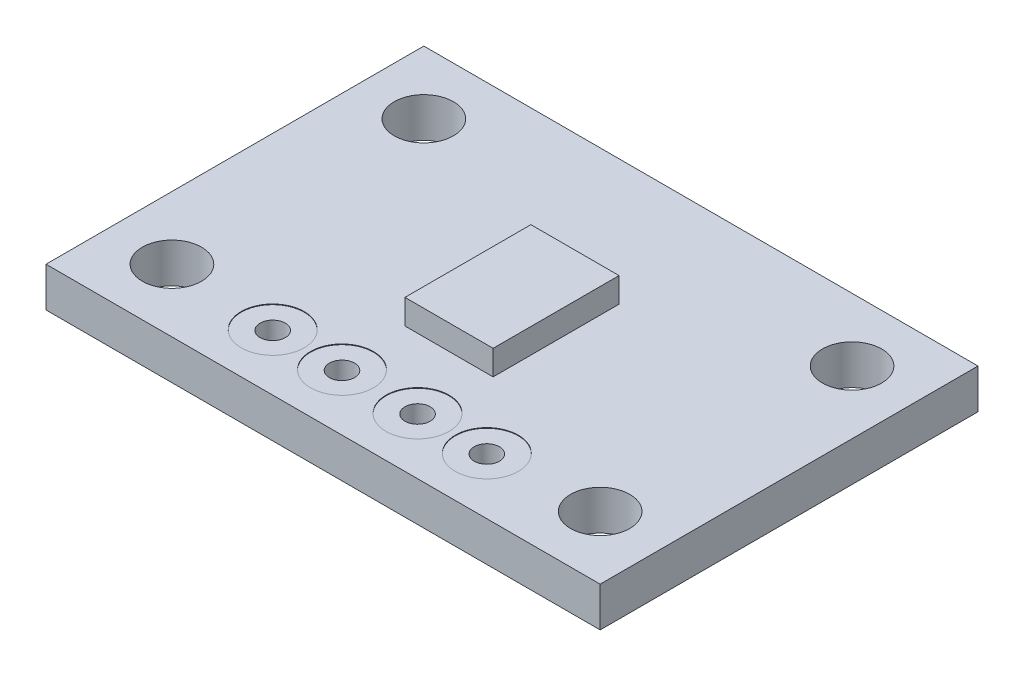
SolidWorks part; units mm, degrees
ref_plane "Front Plane" through (0, 0, 0) normal (0, 0, 1) x (1, 0, 0)
ref_plane "Top Plane" through (0, 0, 0) normal (0, 1, 0) x (1, 0, 0)
ref_plane "Right Plane" through (0, 0, 0) normal (1, 0, 0) x (0, 0, -1)
sketch "Sketch1" plane through (0, 0, 0) normal (0, 1, 0) x (1, 0, 0)
  line L0 (0, 0) -> (0, 50000) construction
  line L1 (-11.176, -7.62) -> (11.176, -7.62)
  line L2 (-11.176, -7.62) -> (-11.176, 7.62)
  line L3 (-11.176, 7.62) -> (11.176, 7.62)
  line L4 (11.176, -7.62) -> (11.176, 7.62)
  line L5 (-11.176, -7.62) -> (11.176, 7.62) construction
  line L6 (-11.176, 7.62) -> (11.176, -7.62) construction
  line L7 (0, 0) -> (50000, 0) construction
  circle A0 centre (8.636, 5.08) radius 1.1938
  circle A1 centre (8.636, -5.08) radius 1.1938
  circle A2 centre (-8.636, -5.08) radius 1.1938
  circle A3 centre (-8.636, 5.08) radius 1.1938
  point P0 (0, 0)
  dimension "D3" = 2.54
  dimension "D4" = 2.54
  dimension "D5" = 2.3876
  dimension "D1" = 22.352
  dimension "D2" = 15.24
extrude "Boss-Extrude1" add sketch "Sketch1" along normal mid plane 1.6
sketch "Sketch2" plane through (0, 0.8, 0) normal (0, 1, 0) x (1, 0, 0)
  line L1 (-1.778, -2.54) -> (1.778, -2.54)
  line L2 (-1.778, -2.54) -> (-1.778, 2.54)
  line L3 (-1.778, 2.54) -> (1.778, 2.54)
  line L4 (1.778, -2.54) -> (1.778, 2.54)
  line L5 (-1.778, -2.54) -> (1.778, 2.54) construction
  line L6 (-1.778, 2.54) -> (1.778, -2.54) construction
  point P0 (0, 0)
  dimension "D1" = 3.556
  dimension "D2" = 5.08
extrude "Boss-Extrude2" add sketch "Sketch2" along normal blind 1
sketch "Sketch3" plane through (0, 0.8, 0) normal (0, 1, 0) x (1, 0, 0)
  line L0 (0, 0) -> (0, 50000) construction
  circle A0 centre (-1.524, -5.334) radius 0.508
  circle A1 centre (-4.318, -5.334) radius 0.508
  circle A2 centre (4.318, -5.334) radius 0.508
  circle A3 centre (1.524, -5.334) radius 0.508
  dimension "D1" = 1.524
  dimension "D2" = 4.318
  dimension "D4" = 1.016
  dimension "D3" = 5.334
extrude "Cut-Extrude1" cut sketch "Sketch3" against normal through all and the other way through all
sketch "Sketch4" plane through (0, 0.8, 0) normal (0, 1, 0) x (1, 0, 0)
  circle A0 centre (-4.318, -5.334) radius 1.27
  circle A1 centre (-1.524, -5.334) radius 1.27
  circle A2 centre (1.524, -5.334) radius 1.27
  circle A3 centre (4.318, -5.334) radius 1.27
  circle A4 centre (1.524, -5.334) radius 0.508 construction
  dimension "D1" = 2.54
extrude "Cut-Extrude2" cut sketch "Sketch4" against normal blind 0.0254
mirror "Mirror1" about plane through (0, 0, 0) normal (0, 1, 0) of "Cut-Extrude2"
ref_axis "Axis1" through (0, 1.93, 0) along (0, -1, 0)
